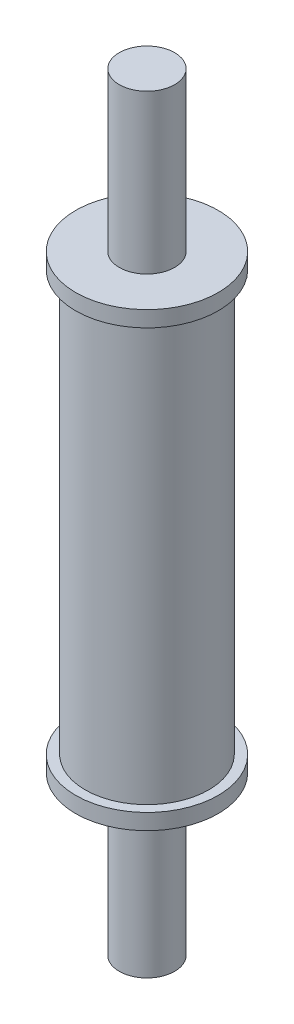
SolidWorks part; units mm, degrees
ref_plane "Front Plane" through (0, 0, 0) normal (0, 0, 1) x (1, 0, 0)
ref_plane "Top Plane" through (0, 0, 0) normal (0, 1, 0) x (1, 0, 0)
ref_plane "Right Plane" through (0, 0, 0) normal (1, 0, 0) x (0, 0, -1)
sketch "Sketch3" plane through (0, 0, 0) normal (0, 1, 0) x (1, 0, 0)
  circle A0 centre (0, 0) radius 9
extrude "Extrude2" add sketch "Sketch3" along normal blind 28.5 and the other way blind 28.5
sketch "Sketch4" plane through (0, 0, 0) normal (0, 1, 0) x (1, 0, 0)
  circle A0 centre (0, 0) radius 7.8
  circle A1 centre (0, 0) radius 9
extrude "Cut-Extrude2" cut sketch "Sketch4" against normal blind 26.5 and the other way blind 26.5
sketch "Sketch5" plane through (0, 0, 0) normal (0, 1, 0) x (1, 0, 0)
  circle A0 centre (0, 0) radius 3.5
extrude "Extrude3" add sketch "Sketch5" along normal blind 48.5 and the other way blind 48.5
sketch "Sketch6" plane through (0, 0, 0) normal (0, 1, 0) x (1, 0, 0)
  circle A0 centre (-51.7394, -9.1972) radius 7.8
  circle A1 centre (-69.6451, -9.1972) radius 7.8
